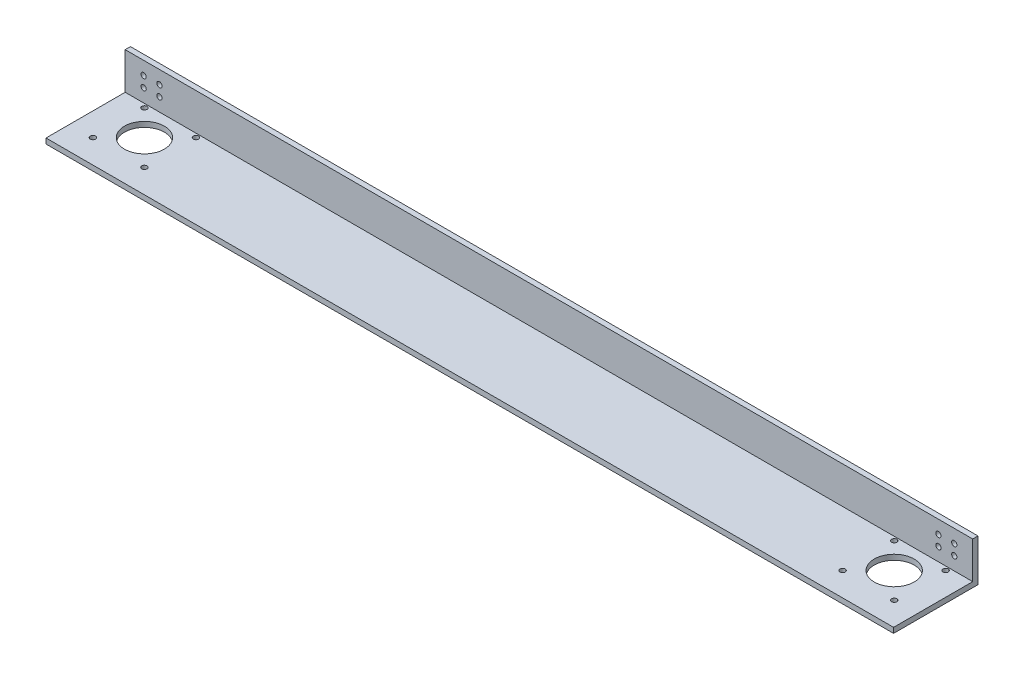
SolidWorks part; units mm, degrees
ref_plane "Front Plane" through (0, 0, 0) normal (0, 0, 1) x (1, 0, 0)
ref_plane "Top Plane" through (0, 0, 0) normal (0, 1, 0) x (1, 0, 0)
ref_plane "Right Plane" through (0, 0, 0) normal (1, 0, 0) x (0, 0, -1)
sketch "Sketch1" plane through (0, 0, 0) normal (1, 0, 0) x (0, 0, -1)
  line L0 (0, 0) -> (-50.8, 0)
  line L1 (-50.8, 0) -> (-50.8, 3.175)
  line L2 (-50.8, 3.175) -> (-3.175, 3.175)
  line L3 (-3.175, 3.175) -> (-3.175, 25.4)
  line L4 (-3.175, 25.4) -> (0, 25.4)
  line L5 (0, 25.4) -> (0, 0)
  dimension "LHeight" = 25.4
  dimension "LWidth" = 50.8
  dimension "LMaterialThickness" = 3.175
  dimension "D1" = 47.625
  dimension "D2" = 22.225
  dimension "D3" = 3.175
extrude "Boss-Extrude1" add sketch "Sketch1" along normal blind 510
sketch "TopHoles-Sketch2" plane through (0, 3.175, 0) normal (0, 1, 0) x (1, 0, 0)
  line L2 (0, -3.175) -> (0, -50.8) construction
  line L3 (510, -3.175) -> (510, -50.8) construction
  circle A0 centre (29.425, -21) radius 12
  circle A1 centre (480.575, -21) radius 12
  circle A2 centre (13.925, -5.5) radius 1.5875
  circle A3 centre (44.925, -5.5) radius 1.5875
  circle A4 centre (465.075, -5.5) radius 1.5875
  circle A5 centre (496.075, -5.5) radius 1.5875
  circle A6 centre (13.925, -36.5) radius 1.5875
  circle A7 centre (44.925, -36.5) radius 1.5875
  circle A8 centre (465.075, -36.5) radius 1.5875
  circle A9 centre (496.075, -36.5) radius 1.5875
  dimension "D9" = 3.175
  dimension "D10" = 24
  dimension "D2" = 5.5
  dimension "D3" = 31
  dimension "D4" = 15.5
  dimension "D5" = 15.5
  dimension "D6" = 31
  dimension "D7" = 15.5
  dimension "D13" = 29.425
  dimension "D8" = 31
  dimension "D11" = 29.425
extrude "TopHoles-Cut-Extrude1" cut sketch "TopHoles-Sketch2" against normal through all
sketch "BackSideHoles-Sketch3" plane through (0, 0, 0) normal (0, 0, -1) x (-1, 0, 0)
  line L1 (-510, 25.4) -> (0, 25.4) construction
  line L2 (0, 0) -> (0, 25.4) construction
  line L3 (-510, 0) -> (-510, 25.4) construction
  circle A0 centre (-498.8875, 17.4625) radius 1.5875
  circle A1 centre (-489.3625, 17.4625) radius 1.5875
  circle A2 centre (-498.8875, 11.1125) radius 1.5875
  circle A3 centre (-489.3625, 11.1125) radius 1.5875
  circle A4 centre (-11.1125, 11.1125) radius 1.5875
  circle A5 centre (-20.6375, 11.1125) radius 1.5875
  circle A6 centre (-20.6375, 17.4625) radius 1.5875
  circle A7 centre (-11.1125, 17.4625) radius 1.5875
  dimension "D7" = 3.175
  dimension "D4" = 11.1125
  dimension "D3" = 7.9375
  dimension "D1" = 11.1125
  dimension "D2" = 20.6375
  dimension "D6" = 20.6375
  dimension "D5" = 11.1125
extrude "BackSideHoles-Cut-Extrude2" cut sketch "BackSideHoles-Sketch3" against normal through all
equation "\"MidBackRailWidth\"= 2.00in"
equation "\"MidBackRailHeight\"= 1.00in"
equation "\"RailThickness\"= .125in'Spec"
equation "\"SideRailHoleY1FromEdge\"= \"HoleOffsetFromEdge\""
equation "\"SideRailHoleX1FromSide\"= \"HoleOffsetFromSide\""
equation "\"StepperHoleDiameter\"= 24mm"
equation "\"StepperMountingHoleDiameter\"= 3.175mm"
equation "\"StepperMountingHoleDistance\"= 31mm'Spec"
equation "\"VSWidth\"= 1.25in'Spec"
equation "\"StepperMountingHoleOffsetFromLeftRightEdge\"= \"StepperMountingHoleOffsetFromItsSide\""
equation "\"HoleOffsetFromEdge\"= \"RailThickness\" * 2.5"
equation "\"HoleOffsetFromSide\"= \"RailThickness\" * 3.5"
equation "\"StepperMountingHoleOffsetFromItsSide\"= 5.5mm'Spec"
equation "\"SideRailHoleX2FromSide\"= \"VSWidth\" - \"HoleOffsetFromEdge\" - \"RailThickness\"'Equals 20.6375"
equation "\"FasteningHoleDiameter\"= .125in"
equation "\"SideRailHoleY2FromSide\"= \"HoleOffsetFromSide\""
equation "\"FrontBackRailLength\"= 510mm"
equation "\"LHeight@Sketch1\"=\"MidBackRailHeight\""
equation "\"LWidth@Sketch1\"=\"MidBackRailWidth\""
equation "\"D2@TopHoles-Sketch2\" = \"StepperMountingHoleOffsetFromLeftRightEdge\""
equation "\"D3@TopHoles-Sketch2\" = \"StepperMountingHoleDistance\""
equation "\"D4@TopHoles-Sketch2\" = \"StepperMountingHoleDistance\" / 2"
equation "\"D5@TopHoles-Sketch2\" = \"StepperMountingHoleDistance\" / 2"
equation "\"D6@TopHoles-Sketch2\" = \"StepperMountingHoleDistance\""
equation "\"D7@TopHoles-Sketch2\" = \"StepperMountingHoleDistance\" / 2"
equation "\"D9@TopHoles-Sketch2\" = \"StepperMountingHoleDiameter\""
equation "\"D10@TopHoles-Sketch2\" = \"StepperHoleDiameter\""
equation "\"D4@BackSideHoles-Sketch3\" = \"SideRailHoleY2FromSide\""
equation "\"D7@BackSideHoles-Sketch3\" = \"FasteningHoleDiameter\""
equation "\"D1@Boss-Extrude1\"= \"FrontBackRailLength\""
equation "\"D3@BackSideHoles-Sketch3\"=\"SideRailHoleY1FromEdge\""
equation "\"D1@BackSideHoles-Sketch3\"=\"SideRailHoleX1FromSide\""
equation "\"D2@BackSideHoles-Sketch3\"= \"SideRailHoleX2FromSide\""
equation "\"D6@BackSideHoles-Sketch3\"=\"SideRailHoleX2FromSide\""
equation "\"D5@BackSideHoles-Sketch3\"=\"SideRailHoleX1FromSide\""
equation "\"StepperHoleToAlignHorizontallyWithGantryBlock\"= \"MidRailToAlignWithGantryBlock\" + \"RailThickness\"'MidSideRail buts up against MidBackRail"
equation "\"D13@TopHoles-Sketch2\"=\"StepperHoleToAlignHorizontallyWithGantryBlock\" "
equation "\"D8@TopHoles-Sketch2\"=\"StepperMountingHoleDistance\""
equation "\"D11@TopHoles-Sketch2\"=\"StepperHoleToAlignHorizontallyWithGantryBlock\" "
equation "\"LinearGBWithRailDepth\"= 12.75mm'Spec"
equation "\"GABDistanceFromBackToFirstPulley\"= 13.5mm"
equation "\"MidRailToAlignWithGantryBlock\"= \"LinearGBWithRailDepth\" + \"GABDistanceFromBackToFirstPulley\"'All outside cogs must align"
